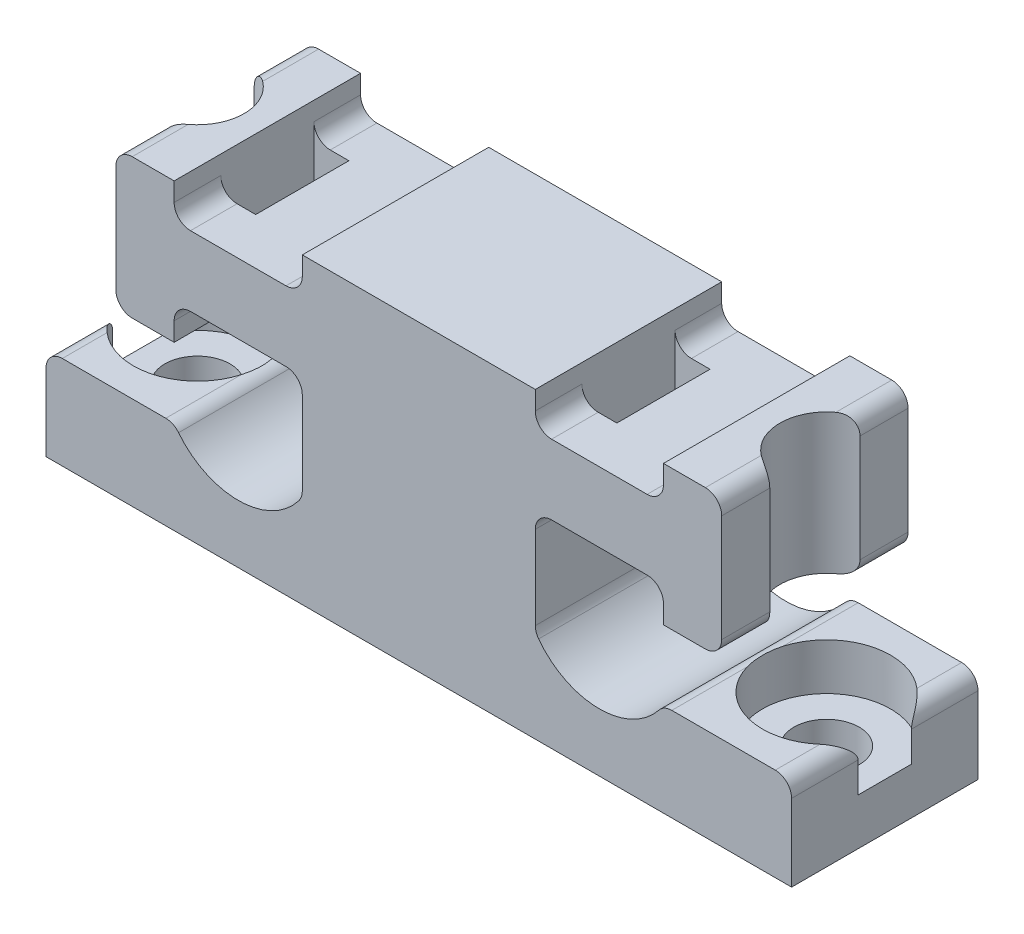
SolidWorks part; units mm, degrees
ref_plane "Front Plane" through (0, 0, 0) normal (0, 0, 1) x (1, 0, 0)
ref_plane "Top Plane" through (0, 0, 0) normal (0, 1, 0) x (1, 0, 0)
ref_plane "Right Plane" through (0, 0, 0) normal (1, 0, 0) x (0, 0, -1)
sketch "Sketch1" plane through (0, 0, 0) normal (0, 0, 1) x (1, 0, 0)
  line L0 (0, 0) -> (0, 13) construction
  line L1 (13, 13) -> (-13, 13)
  line L2 (-13, 13) -> (-13, 7)
  line L3 (-5, 4) -> (-16, 4)
  line L4 (-16, 4) -> (-16, 0)
  line L5 (-16, 0) -> (16, 0)
  line L6 (16, 4) -> (16, 0)
  line L7 (5, 4) -> (16, 4)
  line L8 (13, 13) -> (13, 7)
  line L9 (-13, 7) -> (-5, 7)
  line L18 (-5, 7) -> (-5, 4)
  line L19 (5, 4) -> (5, 7)
  line L20 (5, 7) -> (13, 7)
  dimension "D1" = 32
  dimension "D2" = 26
  dimension "D3" = 4
  dimension "D4" = 13
  dimension "D5" = 10
  dimension "D6" = 3
extrude "Boss-Extrude1" add sketch "Sketch1" along normal blind 8
sketch "Sketch4" plane through (0, 0, 8) normal (0, 0, 1) x (1, 0, 0)
  line L0 (-13, 7) -> (-5, 7) construction
  line L1 (-10.5, 7) -> (-5, 7)
  line L2 (-10.5, 7) -> (-10.5, 8.5)
  line L3 (-10.5, 8.5) -> (-5, 8.5)
  line L4 (-5, 7) -> (-5, 8.5)
  line L5 (13, 13) -> (-13, 13) construction
  line L6 (-10.5, 13) -> (-5, 13)
  line L7 (-10.5, 13) -> (-10.5, 11.5)
  line L8 (-10.5, 11.5) -> (-5, 11.5)
  line L9 (-5, 13) -> (-5, 11.5)
  line L19 (-5, 7) -> (-5, 4) construction
  line L20 (0, 0) -> (0, 13) construction
  line L21 (-13, 13) -> (-13, 7) construction
  line L22 (5, 13) -> (5, 11.5)
  line L23 (10.5, 11.5) -> (5, 11.5)
  line L24 (10.5, 13) -> (10.5, 11.5)
  line L25 (10.5, 13) -> (5, 13)
  line L26 (5, 7) -> (5, 8.5)
  line L27 (10.5, 8.5) -> (5, 8.5)
  line L28 (10.5, 7) -> (10.5, 8.5)
  line L29 (10.5, 7) -> (5, 7)
  dimension "D1" = 1.5
  dimension "D2" = 2.5
  dimension "D3" = 3
extrude "Cut-Extrude2" cut sketch "Sketch4" against normal through all
sketch "Sketch7" plane through (0, 0, 8) normal (0, 0, 1) x (1, 0, 0)
  line L0 (-5, 4) -> (-16, 4) construction
  line L1 (-10.5, 4) -> (-5, 4)
  line L2 (-7.75, 4) -> (-7.75, 8.5) construction
  line L3 (-5, 8.5) -> (-10.5, 8.5) construction
  line L4 (-5, 8.5) -> (-5, 4) construction
  line L5 (0, 0) -> (0, 5.5737) construction
  line L6 (-16, 0) -> (16, 0) construction
  line L7 (10.5, 4) -> (5, 4)
  arc A0 (-10.5, 4) -> (-5, 4) centre (-7.75, 5.7708) ccw
  arc A1 (10.5, 4) -> (5, 4) centre (7.75, 5.7708) cw
  point P9 (-7.75, 2.5)
  dimension "D2" = 1.5
extrude "Cut-Extrude6" cut sketch "Sketch7" against normal through all
fillet "Fillet1" radius 0.7 18 edges at (16, 4, 4) (-16, 4, 4) (-5, 8.5, 4) (-10.5, 8.5, 4) (-13, 7, 4) (-13, 13, 4) (-10.5, 11.5, 4) (-5, 11.5, 4) (5, 11.5, 4) (10.5, 11.5, 4) (13, 13, 4) (13, 7, 4) (10.5, 8.5, 4) (5, 8.5, 4) (-10.5, 4, 4) (-5, 4, 4) (10.5, 4, 4) (5, 4, 4)
sketch "Sketch2" plane through (0, 4, 0) normal (0, 1, 0) x (1, 0, 0)
  line L0 (-13.5, -4) -> (13.5, -4) construction
  line L1 (-16, -8) -> (-16, 0) construction
  circle A0 centre (-13.5, -4) radius 1.4
  circle A1 centre (13.5, -4) radius 1.4
  point P4 (-16, -4)
  point P7 (0, -4)
  dimension "D1" = 2.8
  dimension "D2" = 27
extrude "Cut-Extrude1" cut sketch "Sketch2" against normal through all both and the other way through all
sketch "Sketch5" plane through (0, 13, 0) normal (0, 1, 0) x (1, 0, 0)
  line L0 (-10.5, 0) -> (-10.5, -8) construction
  line L1 (-10.5, -2) -> (-9, -2)
  line L2 (-10.5, -2) -> (-10.5, -6)
  line L3 (-10.5, -6) -> (-9, -6)
  line L4 (-9, -2) -> (-9, -6)
  line L5 (-10.5, -8) -> (-10.5, 0) construction
  line L6 (-5, 0) -> (-5, -8) construction
  line L7 (-5, -2) -> (-6.5, -2)
  line L8 (-5, -2) -> (-5, -6)
  line L9 (-5, -6) -> (-6.5, -6)
  line L10 (-6.5, -2) -> (-6.5, -6)
  line L11 (-9.8, 0) -> (-10.5, 0) construction
  line L12 (0, 0) -> (0, -8) construction
  line L13 (5, 0) -> (-5, 0) construction
  line L14 (5, -8) -> (-5, -8) construction
  line L15 (5, -6) -> (6.5, -6)
  line L16 (6.5, -2) -> (6.5, -6)
  line L17 (5, -2) -> (6.5, -2)
  line L18 (5, -2) -> (5, -6)
  line L19 (10.5, -6) -> (9, -6)
  line L20 (9, -2) -> (9, -6)
  line L21 (10.5, -2) -> (9, -2)
  line L22 (10.5, -2) -> (10.5, -6)
  point P8 (-10.5, -4)
  point P9 (-10.5, -4)
  dimension "D1" = 1.5
  dimension "D2" = 2
  dimension "D3" = 4
extrude "Cut-Extrude3" cut sketch "Sketch5" against normal up to next
sketch "Sketch6" plane through (0, 4, 0) normal (0, 1, 0) x (1, 0, 0)
  circle A0 centre (13.5, -4) radius 2.75
  circle A1 centre (-13.5, -4) radius 2.75
  dimension "D1" = 5.5
extrude "Cut-Extrude5" cut sketch "Sketch6" against normal blind 2
sketch "Sketch8" plane through (0, 2, 0) normal (0, 1, 0) x (1, 0, 0)
  circle A0 centre (-13.5, -4) radius 2
  circle A1 centre (13.5, -4) radius 2
  dimension "D1" = 4
extrude "Cut-Extrude7" cut sketch "Sketch8" along normal through all
